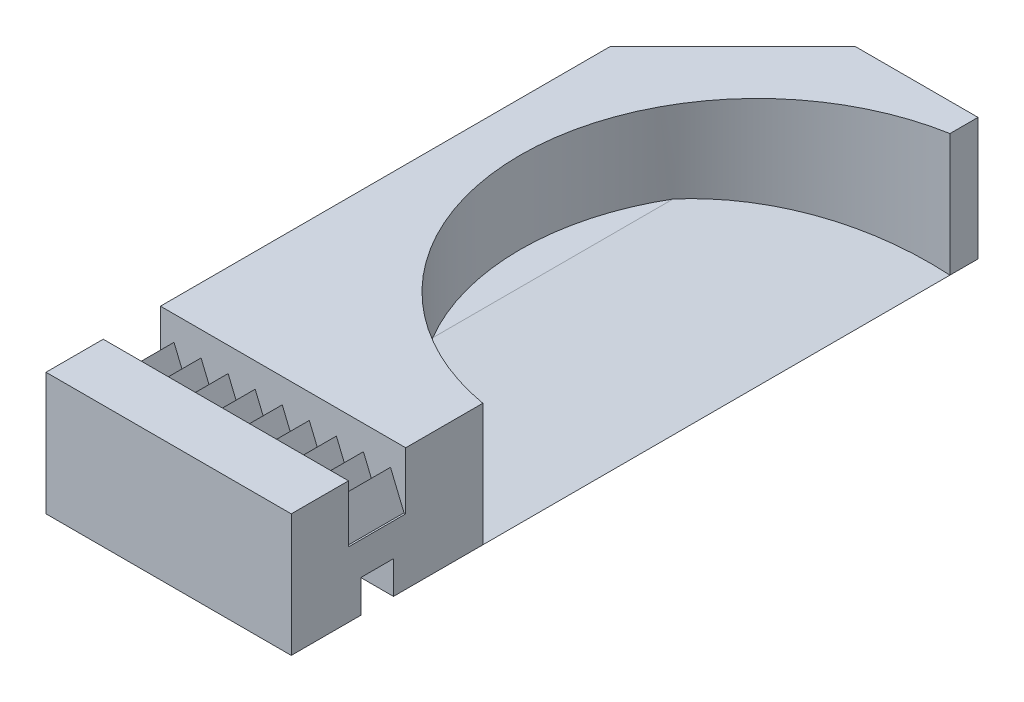
SolidWorks part; units mm, degrees
ref_plane "Plan de face" through (0, 0, 0) normal (0, 0, 1) x (1, 0, 0)
ref_plane "Plan de dessus" through (0, 0, 0) normal (0, 1, 0) x (1, 0, 0)
ref_plane "Plan de droite" through (0, 0, 0) normal (1, 0, 0) x (0, 0, -1)
sketch "Esquisse2" plane through (0, 0, 0) normal (0, 1, 0) x (1, 0, 0)
  line L1 (-32.4129, 40.7804) -> (-2.4129, 40.7804)
  line L2 (-32.4129, 40.7804) -> (-32.4129, -43.2196)
  line L3 (-32.4129, -43.2196) -> (-2.4129, -43.2196)
  line L4 (-2.4129, 40.7804) -> (-2.4129, -43.2196)
  dimension "D1" = 84
  dimension "D2" = 30
extrude "Boss.-Extru.1" add sketch "Esquisse2" along normal blind 15
sketch "Esquisse3" plane through (0, 15, 0) normal (0, 1, 0) x (1, 0, 0)
  line L0 (-2.4129, -43.2196) -> (-2.4129, 40.7804) construction
  line L1 (-32.4129, -43.2196) -> (-2.4129, -43.2196) construction
  circle A0 centre (2.5871, 8.7804) radius 29
  dimension "D1" = 58
  dimension "D2" = 5
  dimension "D3" = 52
extrude "Enlèv. mat.-Extru.1" cut sketch "Esquisse3" against normal blind 10 contours A0
chamfer "Chanfrein1" distance 5 distance2 20 1 edges at (-2.4129, 5, -8.7804) first distance on face at (-2.4129, 8.75, -3.7804)
chamfer "Chanfrein2" distance 15 angle 45 1 edges at (-32.4129, 7.5, -40.7804)
sketch "Esquisse7" plane through (0, 15, 0) normal (0, 1, 0) x (1, 0, 0)
  line L0 (-2.4129, -43.2196) -> (-2.4129, -19.7853) construction
  line L1 (-2.4129, -36.2196) -> (-32.4129, -36.2196)
  line L2 (-2.4129, -36.2196) -> (-2.4129, -29.2196)
  line L3 (-2.4129, -29.2196) -> (-32.4129, -29.2196)
  line L4 (-32.4129, -36.2196) -> (-32.4129, -29.2196)
  line L5 (-32.4129, 25.7804) -> (-32.4129, -43.2196) construction
  dimension "D1" = 7
  dimension "D2" = 7
extrude "Enlèv. mat.-Extru.2" cut sketch "Esquisse7" against normal blind 7 contours L1 L4 L3 L2
sketch "Esquisse8" plane through (0, 0, 29.2196) normal (0, 0, 1) x (1, 0, 0)
  line L0 (-32.4129, 8) -> (-29.0991, 8)
  line L2 (-2.4129, 8) -> (-32.4129, 8) construction
  line L3 (-29.0991, 8) -> (-30.756, 12)
  line L5 (-30.756, 12) -> (-32.4129, 8)
  line L6 (-32.4129, 8) -> (-32.2515, 7.9368)
  dimension "D1" = 67.5
  dimension "D2" = 67.5
  dimension "D3" = 4
extrude "Boss.-Extru.2" add sketch "Esquisse8" along normal blind 7 contours L0 L3 L5
pattern_linear "Répétition linéaire1" count 9 spacing 3.31 along (1, 0, 0) of "Boss.-Extru.2"
sketch "Esquisse9" plane through (-2.4129, 0, 0) normal (1, 0, 0) x (0, 0, -1)
  line L0 (-43.2196, 0) -> (-19.7853, 0) construction
  line L1 (-34.7196, 0) -> (-30.7196, 0)
  line L2 (-34.7196, 0) -> (-34.7196, 4)
  line L3 (-34.7196, 4) -> (-30.7196, 4)
  line L4 (-30.7196, 0) -> (-30.7196, 4)
  line L5 (-43.2196, 15) -> (-43.2196, 0) construction
  dimension "D1" = 4
  dimension "D2" = 4
  dimension "D3" = 8.5
extrude "Enlèv. mat.-Extru.3" cut sketch "Esquisse9" against normal up to next contours L3 L4 L1 L2
sketch3d "Esquisse3D1" plane through (0, 0, 0) normal (0, 0, 1) x (1, 0, 0)
